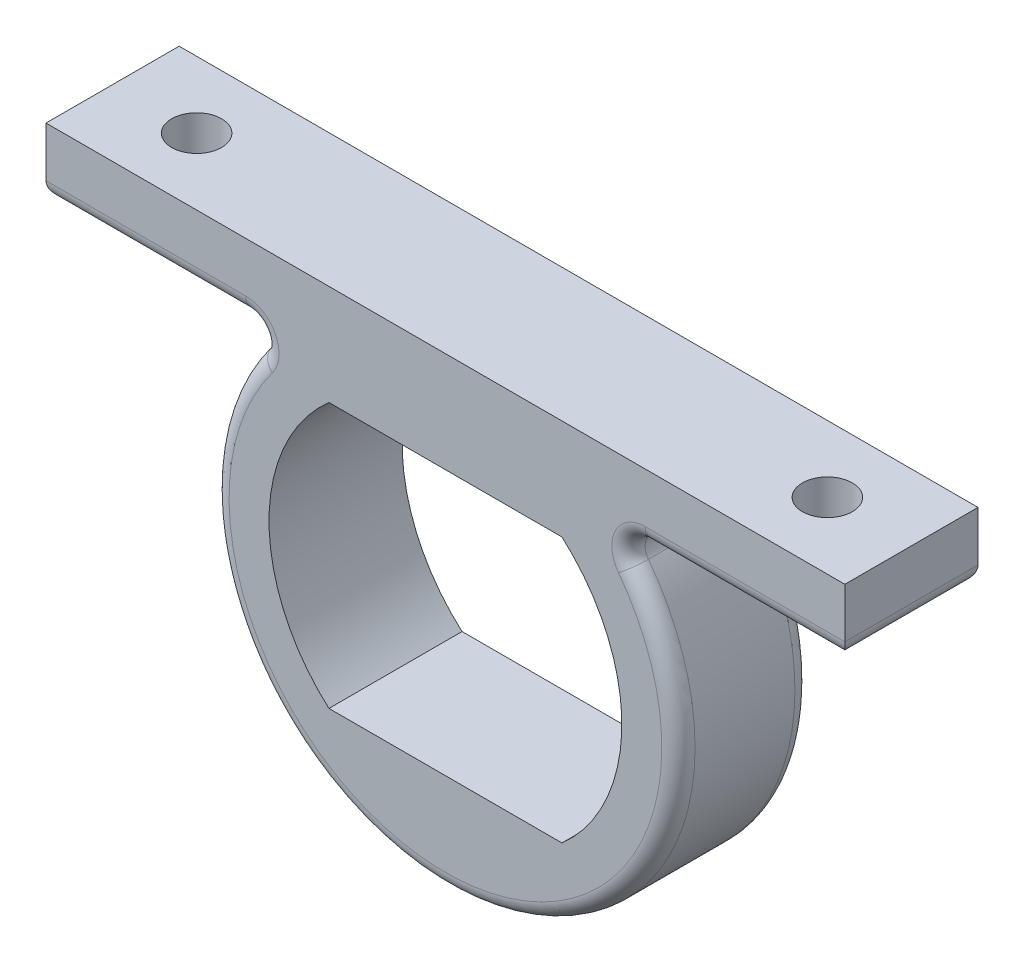
SolidWorks part; units mm, degrees
material "ABS"
ref_plane "Alzado" through (0, 0, 0) normal (0, 0, 1) x (1, 0, 0)
ref_plane "Planta" through (0, 0, 0) normal (0, 1, 0) x (1, 0, 0)
ref_plane "Vista lateral" through (0, 0, 0) normal (1, 0, 0) x (0, 0, -1)
sketch "Croquis1" plane through (0, 0, 0) normal (0, 0, 1) x (1, 0, 0)
  line L0 (0, 14) -> (-24, 14)
  line L1 (-24, 14) -> (-24, 10)
  line L2 (-24, 10) -> (-9.798, 10)
  line L3 (0, 14) -> (24, 14)
  line L4 (24, 14) -> (24, 10)
  line L5 (0, -10) -> (0, 10) construction
  line L6 (24, 10) -> (9.798, 10)
  circle A0 centre (0, 0) radius 10
  arc A1 (-9.798, 10) -> (9.798, 10) centre (0, 0) ccw
  dimension "D1" = 20
  dimension "D2" = 48
  dimension "D5" = 24
  dimension "D4" = 4
  dimension "D3" = 14
extrude "Saliente-Extruir1" add sketch "Croquis1" along normal blind 8 contours L4 L6 A1 L2 L1 L0 L3
sketch "Croquis2" plane through (0, 0, 8) normal (0, 0, 1) x (1, 0, 0)
  line L0 (-7, 7.9599) -> (7, 7.9599)
  line L1 (-7, -7.9599) -> (7, -7.9599)
  arc A0 (-7, 7.9599) -> (-7, -7.9599) centre (0, 0) ccw
  arc A1 (7, 7.9599) -> (7, -7.9599) centre (0, 0) cw
  dimension "D1" = 10.6
  dimension "D2" = 14
  dimension "D4" = 10.6
  dimension "D3" = 14
extrude "Cortar-Extruir1" cut sketch "Croquis2" against normal through all
fillet "Redondeo1" radius 1 10 edges at (-16.899, 10, 8) (-16.899, 10, 0) (16.899, 10, 8) (16.899, 10, 0) (-9.798, 10, 4) (0, -14, 8) (9.798, 10, 4) (0, -14, 0) (24, 10, 4) (-24, 10, 4)
sketch "Croquis3" plane through (0, 10, 0) normal (0, -1, 0) x (-1, 0, 0)
  line L0 (23, -7) -> (23, -1) construction
  line L2 (12, -7) -> (23, -7) construction
  line L4 (-23, -7) -> (-12, -7) construction
  line L5 (-23, -1) -> (-23, -7) construction
  circle A0 centre (18.9495, -4) radius 1.5
  circle A1 centre (-18.9495, -4) radius 1.5
  dimension "D1" = 3
  dimension "D2" = 3
  dimension "D3" = 4.0505
  dimension "D4" = 3
  dimension "D5" = 3
  dimension "D6" = 4.0505
extrude "Cortar-Extruir2" cut sketch "Croquis3" against normal through all
